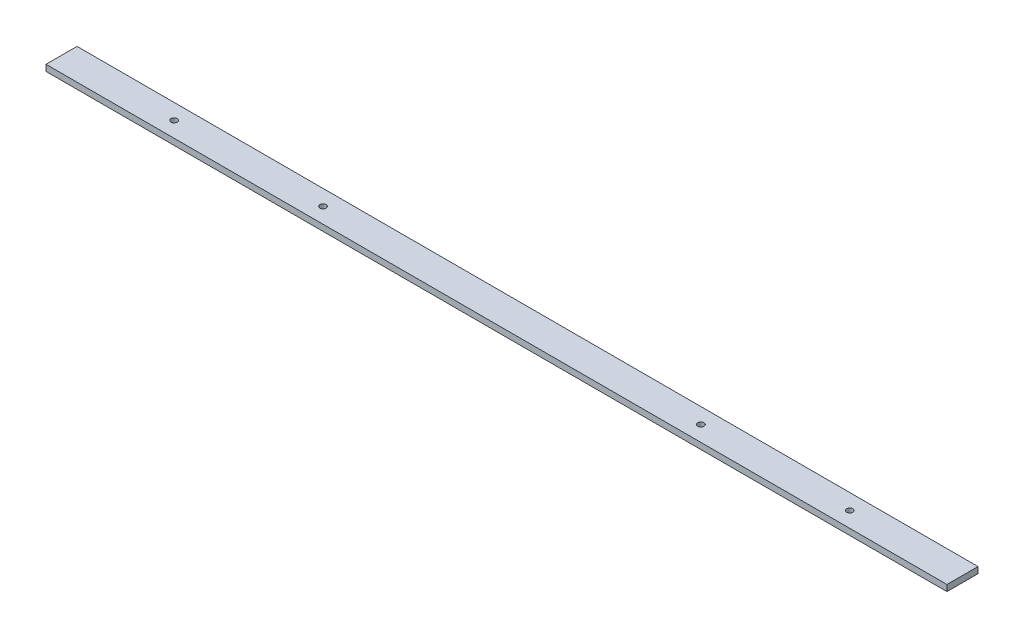
SolidWorks part; units mm, degrees
ref_plane "Front Plane" through (0, 0, 0) normal (0, 0, 1) x (1, 0, 0)
ref_plane "Top Plane" through (0, 0, 0) normal (0, 1, 0) x (1, 0, 0)
ref_plane "Right Plane" through (0, 0, 0) normal (1, 0, 0) x (0, 0, -1)
sketch "Sketch1" plane through (0, 0, 0) normal (0, 1, 0) x (1, 0, 0)
  line L1 (-45.7663, 0) -> (244.5837, 0)
  line L2 (-45.7663, 0) -> (-45.7663, -10)
  line L3 (-45.7663, -10) -> (244.5837, -10)
  line L4 (244.5837, 0) -> (244.5837, -10)
  dimension "D1" = 290.35
  dimension "D2" = 10
base flange "Base-Flange1" sketch "Sketch1" thickness 2 reverse thickness direction no parameters "D1"=0.7366
sketch "Sketch2" plane through (0, 0, 0) normal (0, 1, 0) x (1, 0, 0)
  line L0 (99.4087, 0) -> (99.4087, -10) construction
  line L1 (244.5837, 0) -> (-45.7663, 0) construction
  line L2 (-45.7663, -5) -> (244.5837, -5) construction
  line L3 (-45.7663, 0) -> (-45.7663, -10) construction
  line L4 (244.5837, -10) -> (244.5837, 0) construction
  line L5 (-45.7663, -10) -> (244.5837, -10) construction
  circle A0 centre (-9.4713, -5) radius 1
  circle A1 centre (38.5287, -5) radius 1
  circle A2 centre (160.2887, -5) radius 1
  circle A3 centre (208.2887, -5) radius 1
  dimension "D1" = 2
  dimension "D3" = 2
  dimension "D2" = 36.295
  dimension "D4" = 48
extrude "Cut-Extrude1" cut sketch "Sketch2" against normal blind 10
sketch "Bend-Lines1" [suppressed] plane through (0, 0, 0) normal (0, 1, 0) x (1, 0, 0)
sketch "Bounding-Box1" [suppressed] plane through (0, 0, 0) normal (0, 1, 0) x (1, 0, 0)
sheet metal parameters "Sheet-Metal1" thickness 2 parameters "D1"=0.7366
flat pattern "Flat-Pattern1" [suppressed]
sketch "Bend-Lines2" plane through (0, 0, 0) normal (0, 1, 0) x (1, 0, 0)
sketch3d "Bounding-Box2" [suppressed]
  line L0 (-244.5837, -10, 0) -> (45.7663, -10, 0) construction
  line L1 (-244.5837, 0, 0) -> (45.7663, 0, 0) construction
  line L2 (-244.5837, -10, 0) -> (-244.5837, 0, 0) construction
  line L3 (45.7663, -10, 0) -> (45.7663, 0, 0) construction
sheet metal parameters "Sheet-Metal2" thickness 2 parameters "D1"=0.7366
flat pattern "Flat-Pattern1"
sketch "Bend-Lines2" plane through (0, 0, 0) normal (0, 1, 0) x (1, 0, 0)
sketch3d "Bounding-Box2" [suppressed]
  line L0 (244.5837, -10, 0) -> (-45.7663, -10, 0) construction
  line L1 (244.5837, 0, 0) -> (-45.7663, 0, 0) construction
  line L2 (244.5837, -10, 0) -> (244.5837, 0, 0) construction
  line L3 (-45.7663, -10, 0) -> (-45.7663, 0, 0) construction
